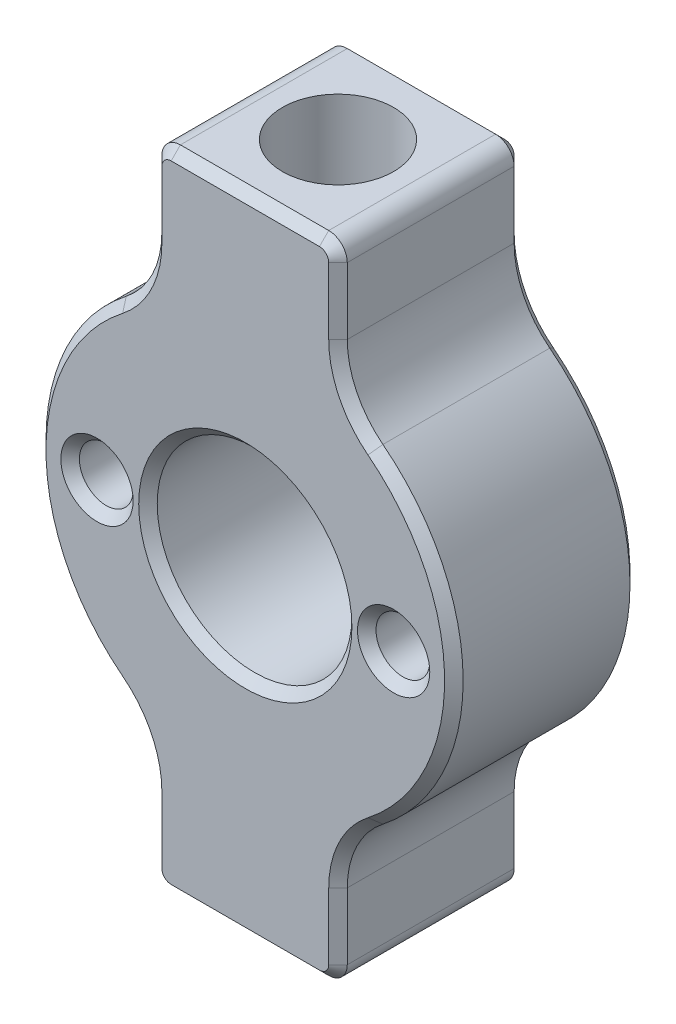
SolidWorks part; units mm, degrees
ref_plane "Front" through (0, 0, 0) normal (0, 0, 1) x (1, 0, 0)
ref_plane "Top" through (0, 0, 0) normal (0, 1, 0) x (1, 0, 0)
ref_plane "Right" through (0, 0, 0) normal (1, 0, 0) x (0, 0, -1)
sketch "Skizze1" plane through (0, 0, 0) normal (0, 0, 1) x (1, 0, 0)
  circle A0 centre (0, 0) radius 5.25
  circle A1 centre (0, 0) radius 11.25
  dimension "D1" = 10.5
  dimension "D2" = 6
extrude "Aufsatz-Linear austragen1" add sketch "Skizze1" along normal blind 10
sketch "Skizze2" plane through (0, 0, 0) normal (0, 1, 0) x (1, 0, 0)
  line L0 (0, 0) -> (0, -10) construction
  line L3 (-11.25, -10) -> (11.25, -10) construction
  line L4 (5.25, 0) -> (-5.25, 0) construction
  line L5 (-5, -10) -> (5, -10)
  line L6 (-5, -10) -> (-5, 0)
  line L7 (-5, 0) -> (5, 0)
  line L8 (5, -10) -> (5, 0)
  line L9 (-5, -10) -> (5, 0) construction
  line L10 (-5, 0) -> (5, -10) construction
  point P4 (0, -5)
extrude "Aufsatz-Linear austragen2" add sketch "Skizze2" along normal blind 11.4 from offset 6
sketch "Skizze3" plane through (0, 17.4, 0) normal (0, 1, 0) x (1, 0, 0)
  line L0 (0, 0) -> (0, -10) construction
  line L1 (-5, -10) -> (5, -10) construction
  circle A0 centre (0, -5) radius 3
  dimension "D1" = 6
extrude "Schnitt-Linear austragen1" cut sketch "Skizze3" against normal blind 10
mirror "Spiegeln1" about plane through (0, 0, 0) normal (0, 1, 0) of "Schnitt-Linear austragen1", "Aufsatz-Linear austragen2"
sketch "Skizze4" plane through (0, 0, 10) normal (0, 0, 1) x (1, 0, 0)
  line L0 (0, 0) -> (0, 11.1324) construction
  line L1 (0, 0) -> (13.0739, 0) construction
  circle A2 centre (8, 0) radius 1.45
  circle A3 centre (-8, 0) radius 1.45
  dimension "D1" = 16
  dimension "D2" = 2.9
extrude "Schnitt-Linear austragen2" cut sketch "Skizze4" against normal blind 8
fillet "Verrundung2" radius 5 4 edges at (-5, -10.0778, 5) (-5, 10.0778, 5) (5, 10.0778, 5) (5, -10.0778, 5)
fillet "Verrundung1" radius 1 4 edges at (-5, 17.4, 5) (5, 17.4, 5) (5, -17.4, 5) (-5, -17.4, 5)
chamfer "Fase1" distance 0.5 angle 45 36 edges at (5.25, 0, 10) (-5, 14.6043, 10) (0, 17.4, 10) (5, 14.6043, 10) (5, -14.6043, 10) (0, -17.4, 10) (-5, -14.6043, 10) (5.25, 0, 0) (5, 14.6043, 0) (0, 17.4, 0) (-5, 14.6043, 0) (-5, -14.6043, 0) (0, -17.4, 0) (5, -14.6043, 0) (5.5064, 10.616, 10) (11.25, 0, 10) (5.5064, -10.616, 10) (-5.5064, -10.616, 10) (-11.25, 0, 10) (-5.5064, 10.616, 10) (5.5064, 10.616, 0) (-5.5064, 10.616, 0) (-11.25, 0, 0) (-5.5064, -10.616, 0) (5.5064, -10.616, 0) (11.25, 0, 0) (-9.45, 0, 10) (9.45, 0, 10) (4.7071, 17.1071, 10) (4.7071, -17.1071, 10) (-4.7071, -17.1071, 10) (-4.7071, 17.1071, 10) (-4.7071, -17.1071, 0) (4.7071, -17.1071, 0) (4.7071, 17.1071, 0) (-4.7071, 17.1071, 0)
